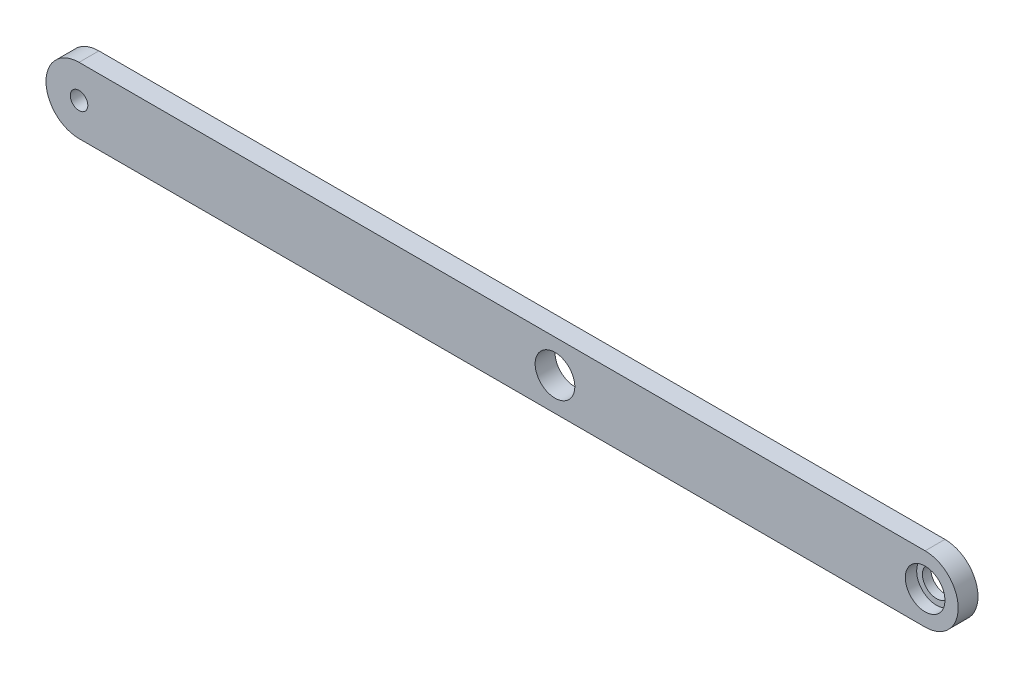
SolidWorks part; units mm, degrees
material "ALUMINUM 6061"
ref_plane "Front Plane" through (0, 0, 0) normal (0, 0, 1) x (1, 0, 0)
ref_plane "Top Plane" through (0, 0, 0) normal (0, 1, 0) x (1, 0, 0)
ref_plane "Right Plane" through (0, 0, 0) normal (1, 0, 0) x (0, 0, -1)
sketch "Sketch1" plane through (0, 0, 0) normal (0, 0, 1) x (1, 0, 0)
  line L0 (-101.6, 0) -> (101.6, 0) construction
  line L1 (-101.6, 7.9375) -> (101.6, 7.9375)
  line L2 (-101.6, -7.9375) -> (101.6, -7.9375)
  arc A0 (-101.6, 7.9375) -> (-101.6, -7.9375) centre (-101.6, 0) ccw
  arc A1 (101.6, -7.9375) -> (101.6, 7.9375) centre (101.6, 0) ccw
  circle A3 centre (101.6, 0) radius 4.7625
  circle A5 centre (101.6, 0) radius 3.3734
  circle A6 centre (12.7, 0) radius 4.7625
  circle A7 centre (-101.6, 0) radius 3.175
  point P2 (0, 0)
  dimension "D3" = 9.525
  dimension "D4" = 6.7469
  dimension "D6" = 6.35
  dimension "D1" = 203.2
  dimension "D2" = 15.875
  dimension "D5" = 88.9
extrude "Boss-Extrude1" add sketch "Sketch1" along normal blind 4.7625 contours L2 A1 L1 A0 A7 A6 A3 | A7 region at (-1.5162, 0, 0) region at (-101.6, 0, 0)
extrude "Boss-Extrude2" add sketch "Sketch1<3>" along normal blind 2.032 contours A3 A5 region at (96.9722, 0, 0)
sketch "Sketch1<3>" plane through (0, 0, 0) normal (0, 0, 1) x (1, 0, 0) same geometry as "Sketch1"
hole_wizard "M5x0.8 Tapped Hole1" positions "Sketch2" profile "Sketch3" tap size "M5x0.8" standard "ANSI Metric"
sketch "Sketch2" plane through (0, 0, 4.7625) normal (0, 0, 1) x (1, 0, 0)
  point P0 (-101.6, 0)
sketch "Sketch3" plane through (-101.6, 0, 4.7625) normal (1, 0, 0) x (0, -1, 0)
  line L0 (0, 0) -> (0, 12.3952)
  line L1 (0, 12.3952) -> (2.1, 11.1334)
  line L2 (2.1, 11.1334) -> (2.1, 0)
  line L5 (2.1, 0) -> (0, 0)
  line L10 (0, 12.3952) -> (-2.1, 11.1334) construction
  line L11 (0, -6.35) -> (0, 107.95) construction
  dimension "Tap Drill Dia." = 4.2
  dimension "Tap Drill Depth" = 12.3952
  dimension "Drill Angle" = 118
cosmetic thread "Hole Thread1"
move or copy body "Body-Move/Copy1" [suppressed] bodies to move or copy 101
equation "\"D4@Sketch1\"=17/64"
